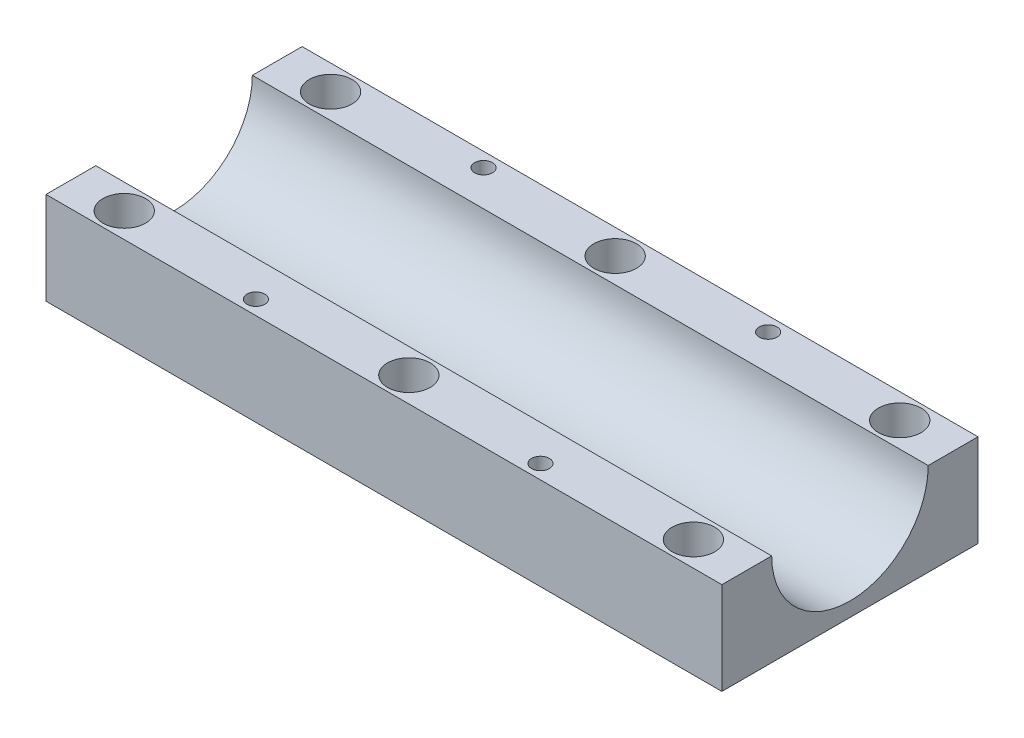
SolidWorks part; units mm, degrees
ref_plane "Спереди" through (0, 0, 0) normal (0, 0, 1) x (1, 0, 0)
ref_plane "Сверху" through (0, 0, 0) normal (0, 1, 0) x (1, 0, 0)
ref_plane "Справа" through (0, 0, 0) normal (1, 0, 0) x (0, 0, -1)
sketch "Эскиз1" plane through (0, 0, 0) normal (0, 1, 0) x (1, 0, 0)
  line L0 (0, 18) -> (95, 18) construction
  line L1 (0, 0) -> (95, 0)
  line L2 (0, 0) -> (0, 36)
  line L3 (0, 36) -> (95, 36)
  line L4 (95, 0) -> (95, 36)
  line L5 (0, 18) -> (0, 29) construction
  line L6 (0, 18) -> (0, 7) construction
  line L7 (0, 7) -> (95, 7) construction
  line L8 (95, 7) -> (95, 29) construction
  line L9 (95, 29) -> (0, 29) construction
  line L10 (0, 36) -> (0, 31) construction
  line L11 (95, 33) -> (95, 36) construction
  circle A0 centre (7.5, 32.5) radius 1.75
  circle A1 centre (47.5, 32.5) radius 1.75
  circle A2 centre (87.5, 32.5) radius 1.75
  circle A3 centre (87.5, 3.5) radius 1.75
  circle A4 centre (47.5, 3.5) radius 1.75
  circle A5 centre (7.5, 3.5) radius 1.75
  point P25 (0, 0)
  point P26 (0, 0)
  point P27 (0, 0)
  point P29 (7.6053, 34)
  point P30 (6.5069, 31.2506)
  dimension "D5" = 3
  dimension "D1" = 95
  dimension "D2" = 36
  dimension "D3" = 22
  dimension "D4" = 7
  dimension "D6" = 40
  dimension "D7" = 3.5
  dimension "D8" = 7.5
extrude "Бобышка-Вытянуть1" add sketch "Эскиз1" along normal blind 13
sketch "Эскиз2" plane through (95, 0, 0) normal (1, 0, 0) x (0, 0, -1)
  line L0 (0, 13) -> (36, 13) construction
  circle A0 centre (18, 13) radius 11
extrude "Вырез-Вытянуть1" cut sketch "Эскиз2" against normal through all
sketch "Эскиз4" plane through (0, 13, 0) normal (0, 1, 0) x (1, 0, 0)
  line L0 (7.5, 32.5) -> (47.5, 32.5) construction
  line L1 (0, 18) -> (95, 18) construction
  line L2 (0, 29) -> (0, 7) construction
  line L3 (95, 7) -> (95, 29) construction
  line L5 (0, 36) -> (0, 29) construction
  line L6 (27.5, 32.5) -> (27.5, 34) construction
  line L7 (95, 36) -> (0, 36) construction
  circle A0 centre (7.5, 32.5) radius 3
  circle A1 centre (47.5, 32.5) radius 3
  circle A2 centre (87.5, 32.5) radius 3
  circle A10 centre (87.5, 3.5) radius 3
  circle A11 centre (47.5, 3.5) radius 3
  circle A12 centre (7.5, 3.5) radius 3
  circle A13 centre (27.5, 34) radius 1.25
  circle A14 centre (67.5, 34) radius 1.25
  circle A15 centre (67.5, 2) radius 1.25
  circle A16 centre (27.5, 2) radius 1.25
  point P30 (0, 0)
  dimension "D1" = 3
  dimension "D3" = 2
  dimension "D6" = 2.5
  dimension "D7" = 6
  dimension "D4" = 27.5
  dimension "D5" = 2
  dimension "D2" = 1
extrude "Вырез-Вытянуть2" cut sketch "Эскиз4" against normal blind 5
